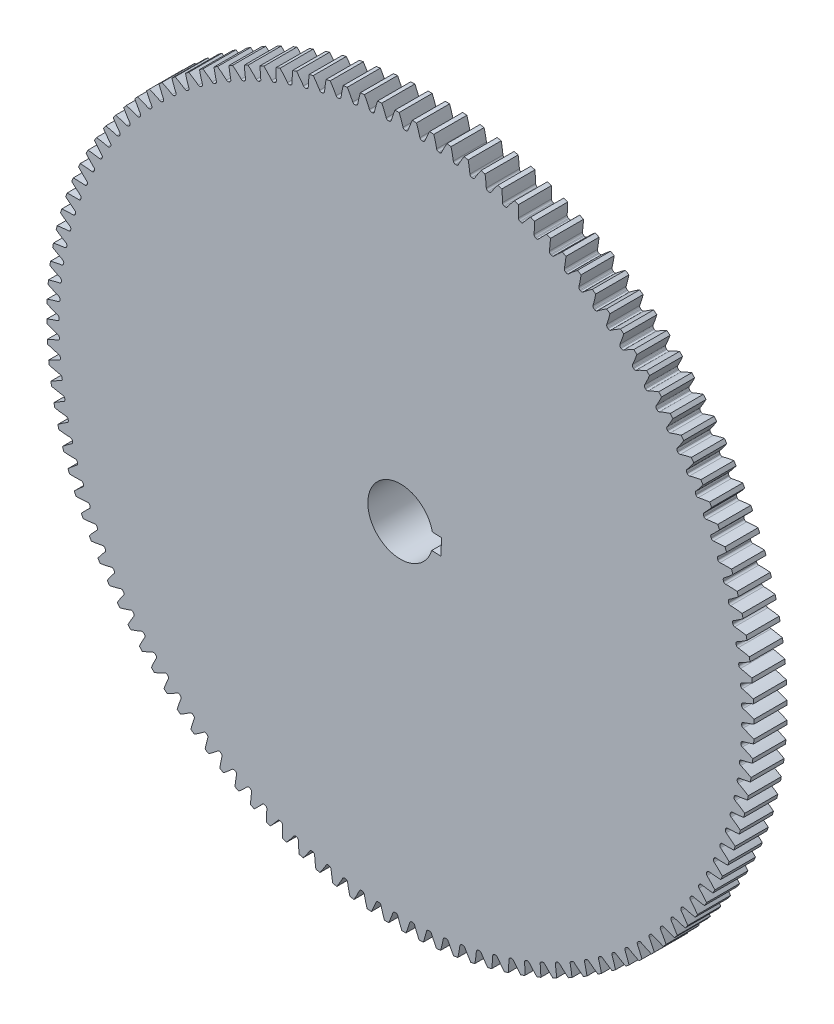
SolidWorks part; units mm, degrees
ref_plane "Front" through (0, 0, 0) normal (0, 0, 1) x (1, 0, 0)
ref_plane "Top" through (0, 0, 0) normal (0, 1, 0) x (1, 0, 0)
ref_plane "Right" through (0, 0, 0) normal (1, 0, 0) x (0, 0, -1)
sketch "Sketch3" plane through (0, 0, 0) normal (0, 0, 1) x (1, 0, 0)
  circle A0 centre (0, 0) radius 51.5938
  dimension "od" = 103.1875
extrude "gearBody" add sketch "Sketch3" along normal blind 4.826
sketch "Sketch2" plane through (0, 0, 0) normal (0, 0, 1) x (1, 0, 0)
  line L0 (0, 0) -> (44.1027, 18.2679) construction
  line L1 (60.0237, -9.0321) -> (0, 0) construction
  line L2 (0, 0) -> (36.3143, 0) construction
  line L3 (50.7999, -0.1147) -> (50.7808, -1.3954) construction
  line L5 (50.7904, -0.7551) -> (0, 0) construction
  line L7 (0, 0) -> (47.7364, 0) construction
  arc A0 (47.7268, -0.958) -> (47.7342, -0.4611) centre (0, 0) ccw construction
  arc A1 (51.5934, 0.1942) -> (51.5648, -1.7277) centre (0, 0) ccw construction
  arc A2 (50.7999, -0.1147) -> (50.7808, -1.3954) centre (0, 0) ccw construction
  arc A3 (49.7903, -0.7978) -> (49.792, -0.6826) centre (0, 0) ccw
  arc A4 (60.0237, -9.0321) -> (50.0047, -1.1051) centre (43.5402, -19.5708) ccw
  arc A5 (60.0237, -9.0321) -> (60.2656, 7.2438) centre (0, 0) ccw
  arc A6 (60.2656, 7.2438) -> (50.0154, -0.3818) centre (44.1027, 18.2679) cw
  arc A7 (49.792, -0.6826) -> (50.0154, -0.3818) centre (50.1122, -0.687) cw
  arc A8 (50.0047, -1.1051) -> (49.7903, -0.7978) centre (50.1105, -0.8029) cw
  point P6 (60.2656, 7.2438)
  point P22 (60.0237, -9.0321)
  dimension "baseDia" = 95.4728
  dimension "od" = 103.1875
  dimension "pd" = 101.6
  dimension "rd" = 99.5934
  dimension "rFillet" = 0.3202
  dimension "pointX" = 60.2656
  dimension "pointY" = 7.2438
  dimension "CTT" = 1.2808
  dimension "flankCenterAngle" = 22.5
extrude "toothCut" cut sketch "Sketch2" along normal through all
pattern_circular "CirPattern1" count 128 over 360 about axis through (0, 0, 4.826) along (0, 0, -1) of "toothCut"
ref_axis "toothSpace" through (0, 0, 0) along (0.9999, -0.0149, 0)
ref_axis "Axis2" through (51.5537, -2.0327, 0) along (-0.9992, 0.0394, 0)
sketch "hub1Dia" plane through (0, 0, 0) normal (0, 0, -1) x (-1, 0, 0)
  circle A0 centre (0, 0) radius 23.876
  dimension "hub1Dia" = 47.752
extrude "hub1" add sketch "hub1Dia" along normal blind 12.7
sketch "hub2Dia" plane through (0, 0, 4.826) normal (0, 0, 1) x (1, 0, 0)
  circle A0 centre (0, 0) radius 12.7
  dimension "hub2dia" = 25.4
sketch "boreDia" plane through (0, 0, 0) normal (0, 0, 1) x (1, 0, 0)
  circle A0 centre (0, 0) radius 4.7625
  dimension "boreDia" = 9.525
extrude "bore" cut sketch "boreDia" against normal mid plane 25400
sketch "kwy1sketch" plane through (0, 0, 0) normal (0, 0, 1) x (1, 0, 0)
  line L0 (-5.3183, 0.2097) -> (0, 0) construction
  line L1 (5.9935, 0.9559) -> (5.8997, -1.4248)
  line L2 (5.8997, -1.4248) -> (2.9238, -1.3075)
  line L3 (5.9935, 0.9559) -> (3.0177, 1.0732)
  line L4 (2.9238, -1.3075) -> (0, 0)
  line L5 (0, 0) -> (3.0177, 1.0732)
  line L6 (0, 0) -> (49.7912, -0.7402) construction
  line L7 (5.9466, -0.2345) -> (0, 0) construction
  arc A7 (49.7903, -0.7978) -> (49.792, -0.6826) centre (0, 0) ccw construction
  point P9 (5.9466, -0.2345)
  point P13 (-0.8871, 0.035)
  dimension "kwy1width" = 2.3825
  dimension "kwy1depth" = 5.9512
  dimension "kwy1angle" = 1.406
  dimension "kwy1Depth2" = 2.9782
extrude "kwy1" cut sketch "kwy1sketch" against normal mid plane 12700
sketch "kwy2sketch" plane through (0, 0, 0) normal (0, 0, 1) x (1, 0, 0)
  line L0 (49.7912, -0.7402) -> (0, 0) construction
  line L1 (0, 0) -> (-2.7012, -2.4962) construction
  line L2 (3.5622, 4.914) -> (5.1792, 3.1642)
  line L3 (5.1792, 3.1642) -> (2.992, 1.1429)
  line L4 (3.5622, 4.914) -> (1.375, 2.8927)
  line L5 (2.992, 1.1429) -> (0, 0)
  line L6 (0, 0) -> (1.375, 2.8927)
  arc A2 (49.7903, -0.7978) -> (49.792, -0.6826) centre (0, 0) ccw construction
  point P10 (4.3707, 4.0391)
  dimension "kwy2angle" = 43.594
  dimension "kwy2Width" = 2.3825
  dimension "kwy2depth" = 5.9512
  dimension "kwy2Depth2" = 2.9782
sketch "kwy3sketch" plane through (0, 0, 0) normal (0, 0, 1) x (1, 0, 0)
  line L0 (49.7912, -0.7402) -> (0, 0) construction
  line L1 (0, 0) -> (-0.1048, -2.6588) construction
  line L2 (-0.9559, 5.9935) -> (1.4248, 5.8997)
  line L3 (1.4248, 5.8997) -> (1.3075, 2.9238)
  line L4 (-0.9559, 5.9935) -> (-1.0732, 3.0177)
  line L5 (1.3075, 2.9238) -> (0, 0)
  line L6 (-1.0732, 3.0177) -> (0, 0)
  point P10 (0.2345, 5.9466)
  dimension "kwy3angle" = 88.594
  dimension "kwy3depth" = 5.9512
  dimension "kwy3width" = 2.3825
  dimension "kwy3Depth2" = 2.9782
sketch "kwy4sketch" plane through (0, 0, 0) normal (0, 0, 1) x (1, 0, 0)
  line L0 (49.7912, -0.7402) -> (0, 0) construction
  line L1 (0, 0) -> (1.412, -1.528) construction
  line L2 (-3.1642, 5.1792) -> (-4.914, 3.5622)
  line L3 (-4.914, 3.5622) -> (-2.8927, 1.375)
  line L4 (-2.8927, 1.375) -> (0, 0)
  line L5 (-1.1429, 2.992) -> (0, 0)
  line L6 (-3.1642, 5.1792) -> (-1.1429, 2.992)
  point P15 (-4.0391, 4.3707)
  dimension "kwy4angle" = 133.594
  dimension "kwy4depth" = 5.9512
  dimension "kwy4width" = 2.3825
  dimension "kwy4Depth2" = 2.9782
sketch "kwy5sketch" plane through (0, 0, 0) normal (0, 0, 1) x (1, 0, 0)
  line L0 (49.7912, -0.7402) -> (0, 0) construction
  line L1 (0, 0) -> (1.7854, -0.0704) construction
  line L2 (-5.8997, 1.4248) -> (-5.9935, -0.9559)
  line L3 (-5.9935, -0.9559) -> (-3.0177, -1.0732)
  line L4 (-5.8997, 1.4248) -> (-2.9238, 1.3075)
  line L5 (-3.0177, -1.0732) -> (0, 0)
  line L6 (-2.9238, 1.3075) -> (0, 0)
  point P10 (-5.9466, 0.2345)
  dimension "kwy5width" = 2.3825
  dimension "kwy5depth" = 5.9512
  dimension "kwy5angle" = 178.594
  dimension "kwy5Depth2" = 2.9782
sketch "kwy6sketch" plane through (0, 0, 0) normal (0, 0, 1) x (1, 0, 0)
  line L0 (49.7912, -0.7402) -> (0, 0) construction
  line L1 (0, 0) -> (1.3112, 1.2117) construction
  line L2 (-5.1792, -3.1642) -> (-3.5622, -4.914)
  line L3 (-3.5622, -4.914) -> (-1.375, -2.8927)
  line L4 (-5.1792, -3.1642) -> (-2.992, -1.1429)
  line L5 (-1.375, -2.8927) -> (0, 0)
  line L6 (-2.992, -1.1429) -> (0, 0)
  point P10 (-4.3707, -4.0391)
  dimension "kwy6angle" = 223.594
  dimension "kwy6width" = 2.3825
  dimension "kwy6depth" = 5.9512
  dimension "kwy6Depth2" = 2.9782
sketch "kwy7sketch" plane through (0, 0, 0) normal (0, 0, 1) x (1, 0, 0)
  line L0 (49.7912, -0.7402) -> (0, 0) construction
  line L1 (0, 0) -> (0.0788, 1.9987) construction
  line L2 (-1.4248, -5.8997) -> (0.9559, -5.9935)
  line L3 (-1.4248, -5.8997) -> (-1.3075, -2.9238)
  line L4 (0.9559, -5.9935) -> (1.0732, -3.0177)
  line L5 (-1.3075, -2.9238) -> (0, 0)
  line L6 (1.0732, -3.0177) -> (0, 0)
  point P10 (-0.2345, -5.9466)
  dimension "kwy7angle" = 88.594
  dimension "kwy7width" = 2.3825
  dimension "kwy7depth" = 5.9512
  dimension "kwy7angle1" = 268.594
  dimension "kwy7Depth2" = 2.9782
sketch "kwy8sketch" plane through (0, 0, 0) normal (0, 0, 1) x (1, 0, 0)
  line L0 (49.7912, -0.7402) -> (0, 0) construction
  line L1 (0, 0) -> (-1.2061, 1.3051) construction
  line L2 (3.1642, -5.1792) -> (4.914, -3.5622)
  line L3 (4.914, -3.5622) -> (2.8927, -1.375)
  line L4 (3.1642, -5.1792) -> (1.1429, -2.992)
  line L5 (2.8927, -1.375) -> (0, 0)
  line L6 (1.1429, -2.992) -> (0, 0)
  point P10 (4.0391, -4.3707)
  dimension "kwy8angle" = 313.594
  dimension "kwy8width" = 2.3825
  dimension "kwy8depth" = 5.9512
  dimension "kwy8Depth2" = 2.9782
sketch "centerLine" plane through (0, 0, 0) normal (0, 1, 0) x (1, 0, 0)
  line L0 (0, 36.4807) -> (0, -59.6309) construction
ref_plane "CB1plane" through (0, 0, -12.7) normal (0, 0, -1) x (-1, 0, 0)
sketch "CB1diameter" plane through (0, 0, -12.7) normal (0, 0, -1) x (-1, 0, 0)
  circle A0 centre (0, 0) radius 12.7
  dimension "CB1diameter" = 25.4
ref_plane "CB2plane" through (0, 0, 4.826) normal (0, 0, 1) x (1, 0, 0)
sketch "CB2diameter" plane through (0, 0, 4.826) normal (0, 0, 1) x (1, 0, 0)
  circle A0 centre (0, 0) radius 12.7
  dimension "CB2diameter" = 25.4
ref_axis "Axis1" through (0, 0, 50) along (0, 0, -1)
sketch3d "3DSketch1" plane through (0, 0, 0) normal (0, 0, 1) x (1, 0, 0)
